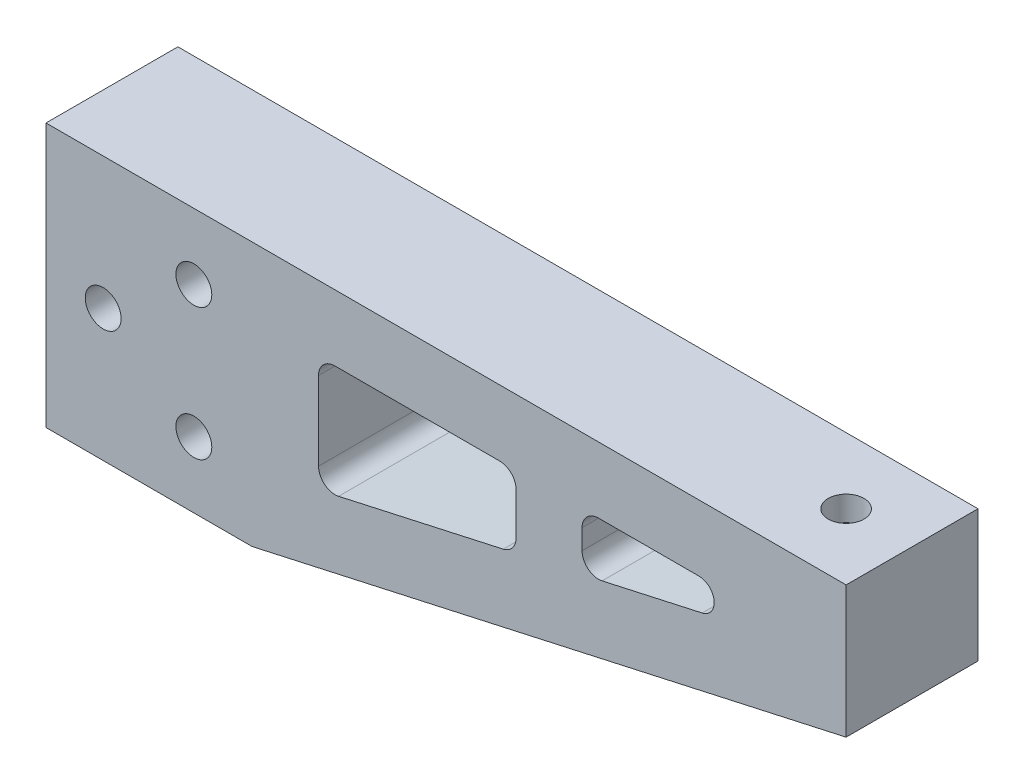
SolidWorks part; units mm, degrees
ref_plane "Front Plane" through (0, 0, 0) normal (0, 0, 1) x (1, 0, 0)
ref_plane "Top Plane" through (0, 0, 0) normal (0, 1, 0) x (1, 0, 0)
ref_plane "Right Plane" through (0, 0, 0) normal (1, 0, 0) x (0, 0, -1)
sketch "Sketch1" plane through (0, 0, 0) normal (0, 0, 1) x (1, 0, 0)
  line L1 (0, 12.7) -> (-77.0433, 12.7)
  line L2 (0, 12.7) -> (0, -12.7)
  line L3 (0, -12.7) -> (-77.0433, -12.7)
  line L4 (-77.0433, 12.7) -> (-77.0433, -12.7)
  point P4 (-0.7993, -12.7)
  point P5 (0, 0)
  point P7 (-72.6476, 12.7)
  point P8 (-179.811, 12.7)
  dimension "D1" = 25.4
  dimension "D2" = 77.0433
extrude "Boss-Extrude1" add sketch "Sketch1" along normal mid plane 12.7
sketch "Sketch2" plane through (0, 12.7, 0) normal (0, 1, 0) x (1, 0, 0)
  line L1 (-3.4013, -2.9487) -> (-9.2988, -2.9487)
  line L2 (-3.4013, -2.9487) -> (-3.4013, 2.9488)
  line L3 (-3.4013, 2.9488) -> (-9.2988, 2.9488)
  line L4 (-9.2988, -2.9487) -> (-9.2988, 2.9488)
  line L5 (-3.4013, -2.9487) -> (-9.2988, 2.9488) construction
  line L6 (-3.4013, 2.9488) -> (-9.2988, -2.9487) construction
  point P0 (-6.35, 0)
  dimension "D1" = 5.8975
extrude "Cut-Extrude1" cut sketch "Sketch2" against normal blind 2.1764 from offset 2.3812 offset against normal yes
hole_wizard "#4 Clearance Hole1" positions "Sketch3" profile "Sketch4" hole size "#4" standard "ANSI Inch"
sketch "Sketch3" plane through (0, 12.7, 0) normal (0, 1, 0) x (1, 0, 0)
  point P0 (-6.35, 0)
sketch "Sketch4" plane through (-6.35, 12.7, 0) normal (1, 0, 0) x (0, 0, 1)
  line L0 (0, 0) -> (0, 7.3878)
  line L1 (0, 7.3878) -> (1.7272, 6.35)
  line L2 (1.7272, 6.35) -> (1.7272, 0)
  line L5 (1.7272, 0) -> (0, 0)
  line L10 (0, 7.3878) -> (-1.7272, 6.35) construction
  line L11 (0, -6.35) -> (0, 107.95) construction
  dimension "Hole Dia." = 3.4544
  dimension "Hole Depth" = 6.35
  dimension "Drill Angle" = 118
hole_wizard "#4 Clearance Hole2" positions "Sketch5" profile "Sketch7" hole size "#4" standard "ANSI Inch" end condition through all
sketch "Sketch5" plane through (0, 0, 6.35) normal (0, 0, 1) x (1, 0, 0)
  point P0 (-62.8066, -6.35)
  point P3 (-71.5378, 0)
  point P6 (-62.8066, 6.35)
sketch "Sketch7" plane through (-62.8066, -6.35, 6.35) normal (1, 0, 0) x (0, -1, 0)
  line L0 (0, 0) -> (0, 12.7)
  line L1 (0, 12.7) -> (1.7272, 12.7)
  line L2 (1.7272, 12.7) -> (1.7272, 0)
  line L5 (1.7272, 0) -> (0, 0)
  line L11 (0, -6.35) -> (0, 107.95) construction
  dimension "Thru Hole Dia." = 3.4544
  dimension "Thru Hole Depth" = 12.7
sketch "Sketch8" plane through (0, 0, -6.35) normal (0, 0, -1) x (-1, 0, 0)
  line L0 (0, 0) -> (0, -12.7)
  line L1 (0, -12.7) -> (0, 12.7) construction
  line L2 (0, -12.7) -> (57.1995, -12.7)
  line L3 (77.0433, -12.7) -> (0, -12.7) construction
  line L4 (57.1995, -12.7) -> (0, 0)
  point P8 (0, 2.8125)
  point P9 (77.9123, -12.7)
  point P10 (81.6385, -12.7)
  point P11 (80.5532, -12.7)
  dimension "D1" = 19.8438
  dimension "D2" = 12.7
extrude "Cut-Extrude2" cut sketch "Sketch8" against normal through all
sketch "Sketch9" plane through (0, 0, 6.35) normal (0, 0, 1) x (1, 0, 0)
  line L0 (-12.7, 3.6849) -> (-25.4248, 0.8596)
  line L1 (-25.4248, 0.8596) -> (-25.4248, 6.35)
  line L2 (-25.4248, 6.35) -> (-12.7, 6.35)
  line L3 (-12.7, 6.35) -> (-12.7, 3.6849)
  line L4 (-31.7748, -0.5503) -> (-50.8016, -4.7748)
  line L5 (-50.8016, -4.7748) -> (-50.8016, 6.35)
  line L6 (-50.8016, 6.35) -> (-31.7748, 6.35)
  line L7 (-31.7748, 6.35) -> (-31.7748, -0.5503)
  line L8 (0, 0) -> (0, 12.7) construction
  line L9 (-57.1516, 12.7) -> (-57.1516, -12.7) construction
  line L10 (-57.1995, -12.7) -> (0, 0) construction
  line L11 (0, 12.7) -> (-77.0433, 12.7) construction
  line L12 (0, 12.7) -> (-57.1995, 12.7) construction
  line L13 (-25.4248, 6.35) -> (-31.7748, 6.35) construction
  point P16 (-28.5998, 6.35)
  point P20 (-28.5998, 12.7)
  dimension "D1" = 12.7
  dimension "D2" = 6.35
  dimension "D3" = 6.35
  dimension "D4" = 6.35
  dimension "D5" = 6.35
  dimension "D6" = 19.8438
extrude "Cut-Extrude3" cut sketch "Sketch9" against normal through all
fillet "Fillet1" radius 1.5875 6 edges at (-50.8016, -4.7748, 0) (-50.8016, 6.35, 0) (-31.7748, 6.35, 0) (-31.7748, -0.5503, 0) (-25.4248, 6.35, 0) (-25.4248, 0.8596, 0)
fillet "Fillet2" 2 edges at (-12.7, 6.35, 0) (-12.7, 3.6849, 0) type full round first side face at (-18.2686, 6.35, 0) second side face at (-18.0966, 2.4867, 0) middle face at (-12.7, 5.0174, 0)
